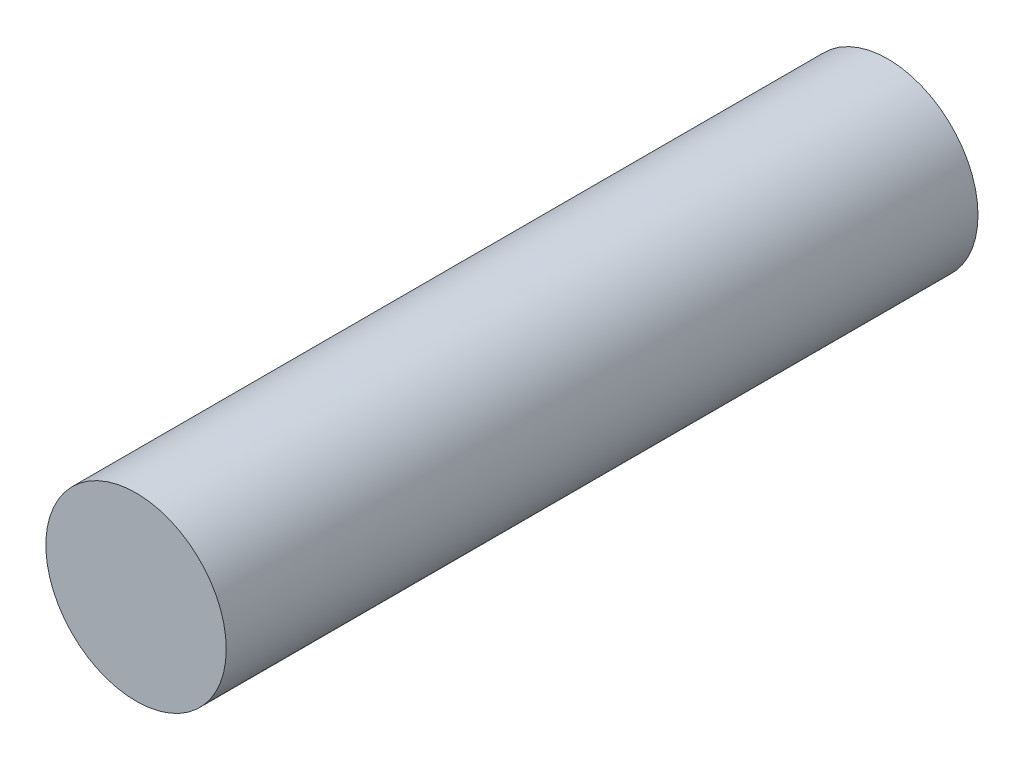
SolidWorks part; units mm, degrees
ref_plane "Plan de face" through (0, 0, 0) normal (0, 0, 1) x (1, 0, 0)
ref_plane "Plan de dessus" through (0, 0, 0) normal (0, 1, 0) x (1, 0, 0)
ref_plane "Plan de droite" through (0, 0, 0) normal (1, 0, 0) x (0, 0, -1)
sketch "Esquisse3" plane through (0, 0, 0) normal (0, 1, 0) x (1, 0, 0)
  line L0 (0, -50) -> (0, 50)
  line L1 (0, 50) -> (-12, 50)
  line L2 (-12, 50) -> (-12, -50)
  line L3 (-12, -50) -> (0, -50)
  dimension "D1" = 12
  dimension "D2" = 100
revolve "cylindre primitif" add sketch "Esquisse3" angle 360 about L0
ref_axis "Axe de la vis sans fin" through (0, 0, -98.8277) along (0, 0, 1)
